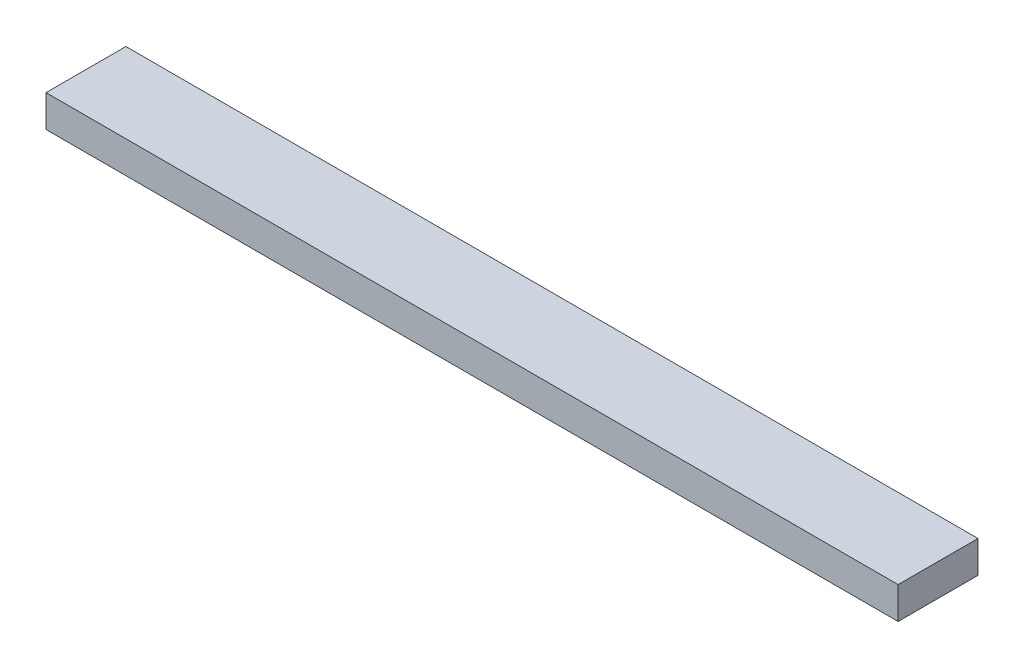
SolidWorks part; units mm, degrees
ref_plane "Front Plane" through (0, 0, 0) normal (0, 0, 1) x (1, 0, 0)
ref_plane "Top Plane" through (0, 0, 0) normal (0, 1, 0) x (1, 0, 0)
ref_plane "Right Plane" through (0, 0, 0) normal (1, 0, 0) x (0, 0, -1)
sketch "Sketch2" plane through (0, 0, 0) normal (0, 1, 0) x (1, 0, 0)
  line L11 (-80, 7.5) -> (80, 7.5)
  line L12 (-80, 7.5) -> (-80, -7.5)
  line L13 (-80, -7.5) -> (80, -7.5)
  line L14 (80, 7.5) -> (80, -7.5)
  dimension "D2" = 80
  dimension "D1" = 160
  dimension "D3" = 15
  dimension "D4" = 7.5
extrude "Boss-Extrude1" add sketch "Sketch2" along normal blind 6
